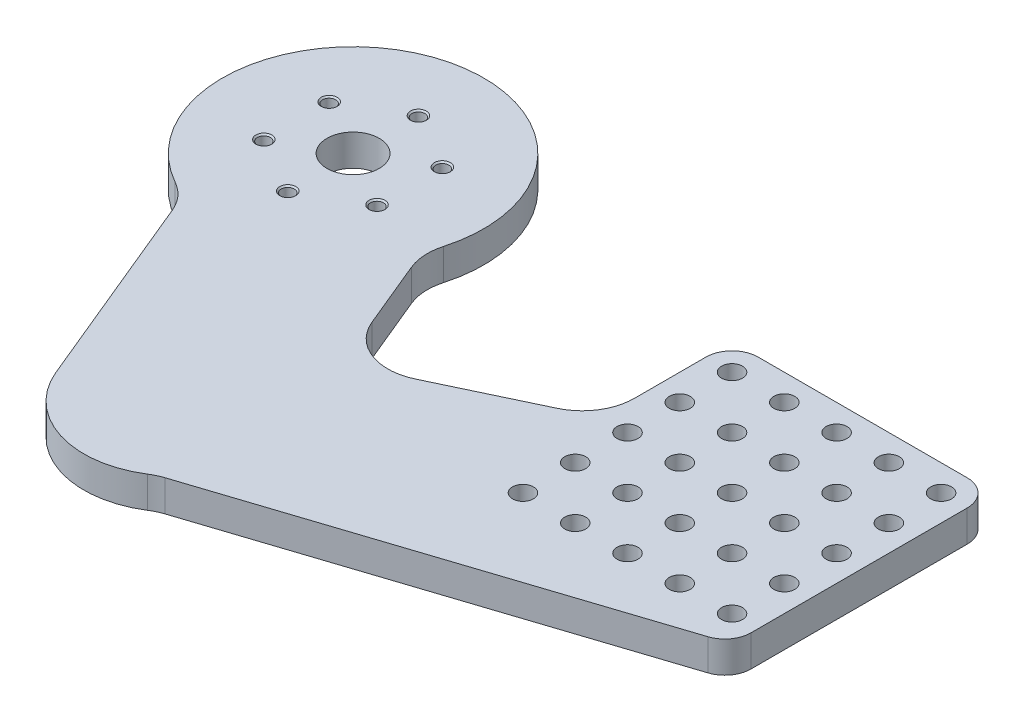
SolidWorks part; units mm, degrees
ref_plane "Front Plane" through (0, 0, 0) normal (0, 0, 1) x (1, 0, 0)
ref_plane "Top Plane" through (0, 0, 0) normal (0, 1, 0) x (1, 0, 0)
ref_plane "Right Plane" through (0, 0, 0) normal (1, 0, 0) x (0, 0, -1)
sketch "Sketch1" plane through (0, 0, 0) normal (0, 1, 0) x (1, 0, 0)
  line L0 (0, -25) -> (0, 20)
  line L1 (-25, 25) -> (25, 25)
  line L2 (-25, 25) -> (-25, -25)
  line L3 (-25, -25) -> (25, -25)
  line L4 (25, 25) -> (25, -25)
  line L5 (-25, 25) -> (25, -25) construction
  line L6 (-25, -25) -> (25, 25) construction
  line L7 (0, 20) -> (-25, 20)
  line L8 (-25, 20) -> (-92.5, 20)
  line L9 (-92.5, 20) -> (-75.2792, -21.5746)
  line L10 (-75.2792, -21.5746) -> (-69.3361, -35.9227)
  line L11 (-68.4521, -55.5568) -> (25, -25)
  line L12 (-76.3321, 26.697) -> (-108.6679, 13.303)
  line L13 (-108.6679, 13.303) -> (-84.62, -44.7537)
  line L14 (-76.3321, 26.697) -> (-52.2842, -31.3598)
  line L15 (-84.62, -44.7537) -> (-52.2842, -31.3598)
  line L16 (-68.4521, -20.5568) -> (-25, 0)
  line L17 (-25, 0) -> (25, -25)
  line L18 (-46.7261, -10.2784) -> (-32.7998, -43.8993)
  line L19 (-32.7998, -43.8993) -> (-25, -25)
  circle A0 centre (-92.5, 20) radius 25
  circle A1 centre (-68.4521, -38.0568) radius 17.5
  point P0 (0, 0)
  point P16 (-92.5, 20)
  dimension "D4" = 67.5
  dimension "D1" = 50
  dimension "D2" = 50
  dimension "D3" = 67.5
  dimension "D5" = 35
extrude "Boss-Extrude1" add sketch "Sketch1" along normal blind 6 contours L19 L11 L3 | L18 L19 L2 L16 | A1 L11 L18 L16 L14 | L11 A1 L15 | L11 A1 | L15 A1 | A1 L14 L16 | A1 L16 L14 A0 L9 | A1 L9 A0 L13 | L17 L2 L3 L0 | L2 L17 L0 L7 | L0 L17 L4 L1 L2 L7 | L17 L0 L3 | L13 A0 L9 L12 | L9 A0 L14 L8 | L8 A0 L13 L12 L14 | L14 A0 L8 | L14 L12 L8 region at (-13.8889, 0, 15.2778) region at (-10.9333, 0, 31.2998) region at (8.3333, 0, 20.8333) region at (-11.5079, 0, -6.627) region at (10.4701, 0, -4.9786) region at (-33.5204, 0, 18.9547) region at (-46.4029, 0, 31.4335) region at (-63.1747, 0, 54.1967) region at (-65.6422, 0, 44.7952) region at (-69.9937, 0, -16.5633) region at (-96.2461, 0, -27.5597) region at (-70.8115, 0, 8.2301) region at (-59.8766, 0, 20.8289) region at (-80.3605, 0, -10.7444) region at (-80.7967, 0, -22.2323) region at (-87.7434, 0, 17.1502) region at (-95.7829, 0, -6.2132) region at (-68.6108, 0, 37.6737)
sketch "Sketch2" plane through (0, 6, 0) normal (0, 1, 0) x (1, 0, 0)
  line L1 (-20, 20) -> (20, 20)
  line L2 (-20, 20) -> (-20, -20)
  line L3 (-20, -20) -> (20, -20)
  line L4 (20, 20) -> (20, -20)
  line L5 (-20, 20) -> (20, -20) construction
  line L6 (-20, -20) -> (20, 20) construction
  circle A0 centre (-20, -20) radius 2
  circle A1 centre (-10, -20) radius 2
  circle A2 centre (0, -20) radius 2
  circle A3 centre (10, -20) radius 2
  circle A4 centre (20, -20) radius 2
  circle A5 centre (-10, -10) radius 2
  circle A6 centre (0, -10) radius 2
  circle A7 centre (10, -10) radius 2
  circle A8 centre (20, -10) radius 2
  circle A9 centre (-10, 0) radius 2
  circle A10 centre (0, 0) radius 2
  circle A11 centre (10, 0) radius 2
  circle A12 centre (20, 0) radius 2
  circle A13 centre (-10, 10) radius 2
  circle A14 centre (0, 10) radius 2
  circle A15 centre (10, 10) radius 2
  circle A16 centre (20, 10) radius 2
  circle A17 centre (-10, 20) radius 2
  circle A18 centre (0, 20) radius 2
  circle A19 centre (10, 20) radius 2
  circle A20 centre (20, 20) radius 2
  circle A21 centre (-20, -10) radius 2
  circle A22 centre (-20, 0) radius 2
  circle A23 centre (-20, 10) radius 2
  circle A24 centre (-20, 20) radius 2
  point P0 (0, 0)
  dimension "D3" = 5
  dimension "D1" = 40
  dimension "D2" = 40
  dimension "D4" = 5
extrude "Cut-Extrude1" cut sketch "Sketch2" against normal blind 10 contours A4 | A0 | A24 | A20 | A1 | A2 | A3 | A8 | A7 | A6 | A5 | A21 | A22 | A23 | A13 | A9 | A10 | A14 | A18 | A17 | A19 | A15 | A11 | A12 | A16
fillet "Fillet5" radius 5 3 edges at (25, 3, 25) (25, 3, -25) (-25, 3, -25)
fillet "Fillet6" radius 10 5 edges at (-69.4998, 3, -10.2024) (-101.8356, 3, 3.1915) (-25, 3, 0) (-58.6749, 3, 15.9313) (-58.1133, 3, 52.1762)
sketch "Sketch5" plane through (0, 6, 0) normal (0, 1, 0) x (1, 0, 0)
  circle A0 centre (-92.5, 20) radius 12.5
  circle A1 centre (-92.5, 32.5) radius 1.2
  circle A2 centre (-81.6747, 26.25) radius 1.2
  circle A3 centre (-92.5, 20) radius 12.5
  circle A4 centre (-81.6747, 13.75) radius 1.2
  circle A5 centre (-92.5, 20) radius 12.5
  circle A6 centre (-92.5, 7.5) radius 1.2
  circle A7 centre (-92.5, 20) radius 12.5
  circle A8 centre (-103.3253, 13.75) radius 1.2
  circle A9 centre (-92.5, 20) radius 12.5
  circle A10 centre (-103.3253, 26.25) radius 1.2
  circle A11 centre (-92.5, 20) radius 12.5
  point P3 (-92.5, 32.5)
  point P9 (-81.6747, 26.25)
  point P12 (-81.6747, 13.75)
  point P15 (-92.5, 7.5)
  point P18 (-103.3253, 13.75)
  point P21 (-103.3253, 26.25)
  dimension "D1" = 6
hole_wizard "M3 Tapped Hole1" positions "Sketch5" profile "Sketch6" tap size "M3" standard "ISO" end condition through all
sketch "Sketch6" plane through (-103.3253, 6, -26.25) normal (1, 0, 0) x (0, 0, 1)
  line L0 (0, 0) -> (0, 6)
  line L1 (0, 6) -> (1.25, 6)
  line L2 (1.25, 6) -> (1.25, 0.275)
  line L3 (1.25, 0.275) -> (1.525, 0)
  line L5 (1.525, 0) -> (0, 0)
  line L6 (-1.25, 0.275) -> (-1.525, 0) construction
  line L11 (0, -6.35) -> (0, 107.95) construction
  dimension "Thru Tap Drill Dia." = 2.5
  dimension "Thru Tap Drill Depth" = 6
  dimension "Near C'Sink Dia." = 3.05
  dimension "Near C'Sink Angle" = 90
cosmetic thread "Hole Thread1" parameters "D2"=3
cosmetic thread "Hole Thread2" parameters "D2"=3
cosmetic thread "Hole Thread3" parameters "D2"=3
cosmetic thread "Hole Thread4" parameters "D2"=3
cosmetic thread "Hole Thread5" parameters "D2"=3
cosmetic thread "Hole Thread6" parameters "D2"=3
sketch "Sketch7" plane through (0, 6, 0) normal (0, 1, 0) x (1, 0, 0)
  circle A0 centre (-92.5, 20) radius 5
extrude "Cut-Extrude2" cut sketch "Sketch7" against normal blind 20.7
